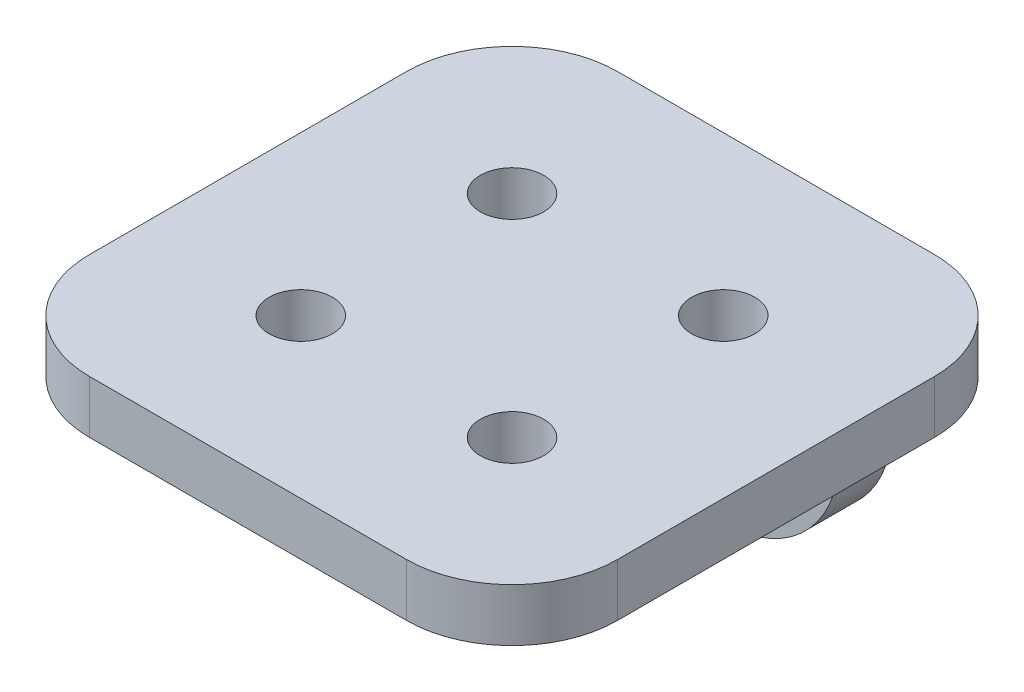
SolidWorks part; units mm, degrees
ref_plane "Front Plane" through (0, 0, 0) normal (0, 0, 1) x (1, 0, 0)
ref_plane "Top Plane" through (0, 0, 0) normal (0, 1, 0) x (1, 0, 0)
ref_plane "Right Plane" through (0, 0, 0) normal (1, 0, 0) x (0, 0, -1)
sketch "Sketch1" plane through (0, 0, 0) normal (0, 0, 1) x (1, 0, 0)
  line L6 (-25, 11) -> (-25, 16)
  line L7 (-25, 16) -> (25, 16)
  line L8 (25, 16) -> (25, 11)
  line L9 (-25, 11) -> (-15, 11)
  line L13 (15, 11) -> (25, 11)
  line L14 (-15, 11) -> (-11, 0)
  line L15 (15, 11) -> (11, 0)
  circle A0 centre (0, 0) radius 11
  circle A1 centre (0, 0) radius 5
  circle A2 centre (0, 8) radius 2
  circle A3 centre (8, 0) radius 2
  circle A4 centre (0, -8) radius 2
  circle A5 centre (-8, 0) radius 2
  circle A6 centre (0, 0) radius 4
  point P15 (0, 0)
  dimension "D1" = 4
  dimension "D2" = 8
  dimension "D3" = 8
  dimension "D5" = 4
  dimension "D4" = 10
  dimension "D6" = 22
  dimension "D7" = 5
  dimension "D8" = 50
  dimension "D9" = 11.7047
  dimension "D10" = 11.7047
  dimension "D11" = 10
  dimension "D12" = 16
extrude "Boss-Extrude2" add sketch "Sketch1" along normal blind 5 contours A0 A5 A4 A3 A2 A1 region at (0, 10.6889, 0)
extrude "Boss-Extrude4" add sketch "Sketch1<9>" along normal blind 5 contours A0 L14 | A0 L15 region at (0, 11.9715, 0)
sketch "Sketch1<9>" plane through (0, 0, 0) normal (0, 0, 1) x (1, 0, 0) same geometry as "Sketch1"
sketch "Sketch2" plane through (0, 0, 5) normal (0, 0, 1) x (1, 0, 0)
  line L0 (-25, 11) -> (-25, 16)
  line L1 (-25, 16) -> (25, 16)
  line L2 (25, 16) -> (25, 11)
  line L3 (25, 11) -> (-25, 11)
extrude "Boss-Extrude7" add sketch "Sketch2" along normal blind 45
sketch "Sketch3" plane through (0, 16, 0) normal (0, 1, 0) x (1, 0, 0)
  line L0 (-25, 0) -> (25, 0) construction
  line L1 (25, -50) -> (-25, -50) construction
  line L2 (-25, -50) -> (-25, 0) construction
  line L3 (25, -50) -> (25, 0) construction
  circle A0 centre (10, -35) radius 3
  circle A1 centre (-10, -35) radius 3
  circle A2 centre (-10, -15) radius 3
  circle A3 centre (10, -15) radius 3
  dimension "D1" = 6
  dimension "D2" = 6
  dimension "D3" = 6
  dimension "D4" = 6
  dimension "D9" = 15
  dimension "D5" = 15
  dimension "D6" = 15
  dimension "D7" = 15
  dimension "D8" = 15
  dimension "D10" = 15
  dimension "D11" = 15
  dimension "D12" = 15
extrude "Cut-Extrude1" cut sketch "Sketch3" against normal up to next
fillet "Fillet1" radius 10 4 edges at (25, 13.5, 0) (-25, 13.5, 0) (-25, 13.5, 50) (25, 13.5, 50)
